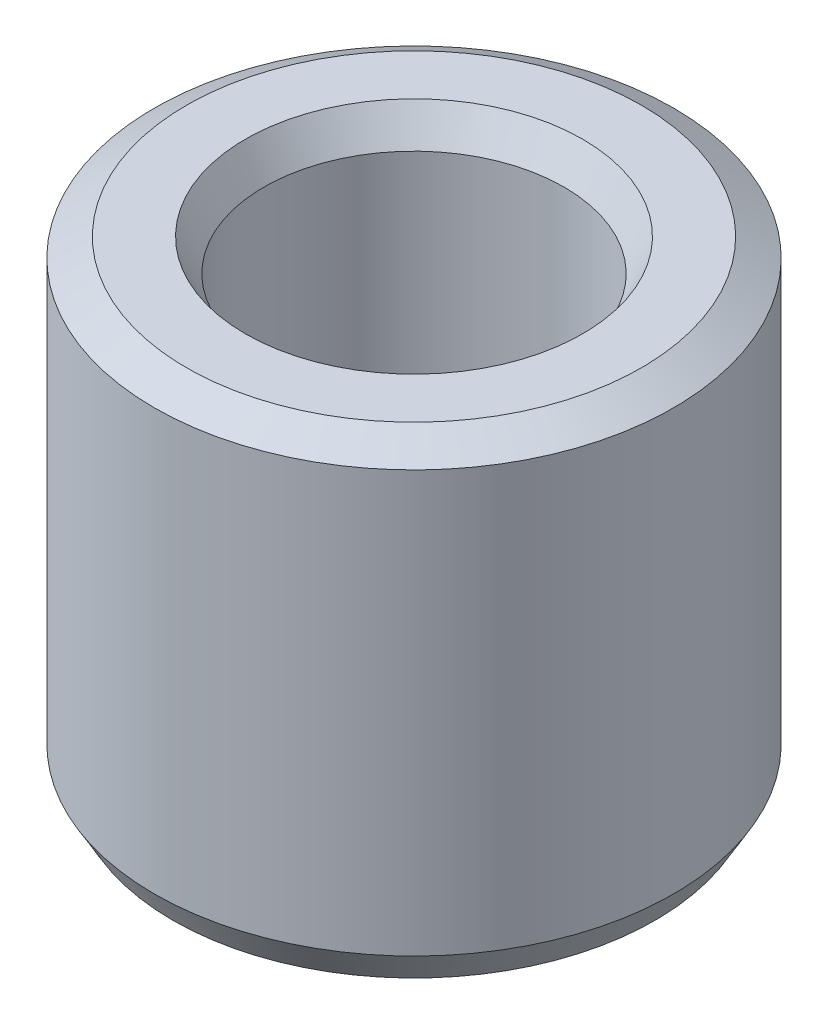
SolidWorks part; units mm, degrees
ref_plane "Front Plane" through (0, 0, 0) normal (0, 0, 1) x (1, 0, 0)
ref_plane "Top Plane" through (0, 0, 0) normal (0, 1, 0) x (1, 0, 0)
ref_plane "Right Plane" through (0, 0, 0) normal (1, 0, 0) x (0, 0, -1)
sketch "Sketch1" plane through (0, 0, 0) normal (0, 1, 0) x (1, 0, 0)
  circle A0 centre (0, 0) radius 47.5
  dimension "SLEEVE_OD" = 95
extrude "Boss-Extrude1" add sketch "Sketch1" along normal blind 86.3137
sketch "Sketch2" plane through (0, 0, 0) normal (0, 1, 0) x (1, 0, 0)
  circle A0 centre (0, 0) radius 27.4523
  dimension "BORE_D" = 54.9046
extrude "Cut-Extrude1" cut sketch "Sketch2" along normal through all
chamfer "Chamfer1" distance 3.3999 angle 60 4 edges at (0, 86.3137, 27.4523) (0, 0, 27.4523) (0, 0, 47.5) (0, 86.3137, 47.5) first distance on face at (0, 86.3137, 27.4523) first distance on face at (0, 0, 27.4523) first distance on face at (0, 86.3137, 47.5)
